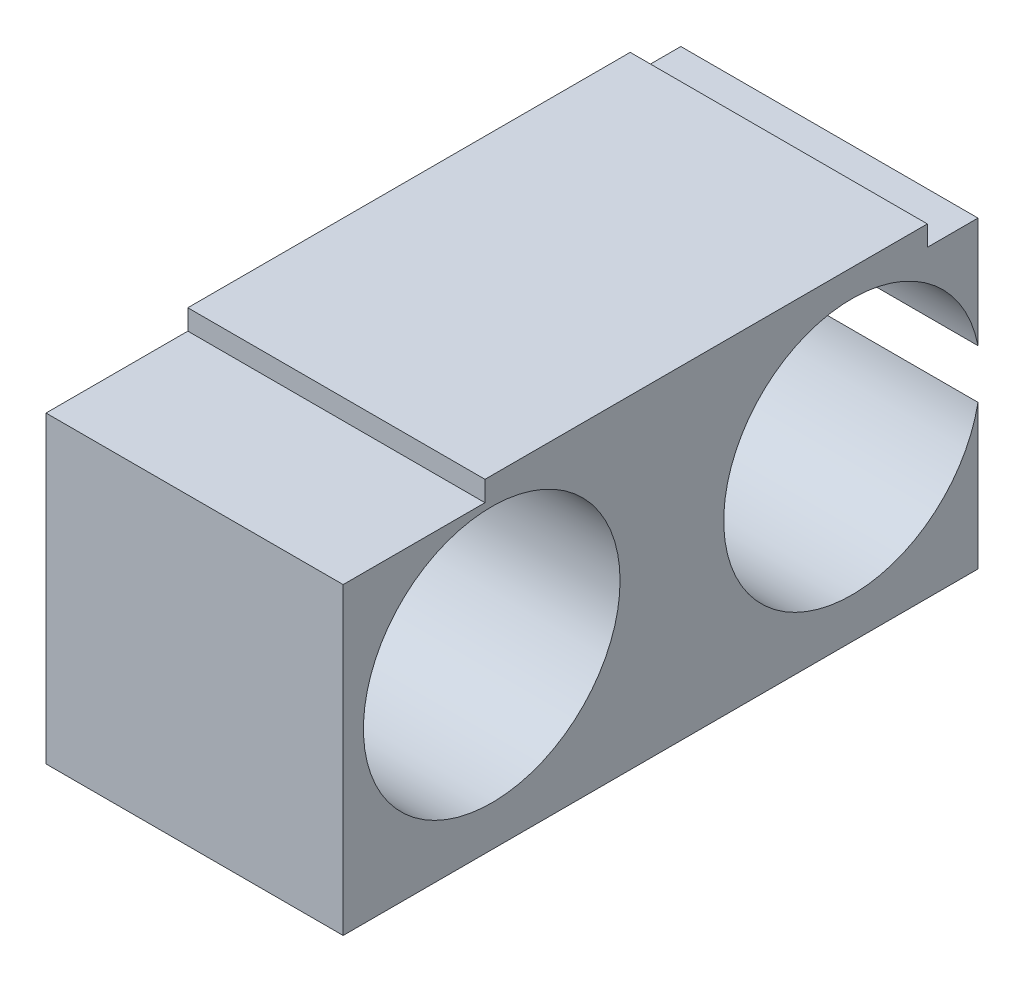
SolidWorks part; units mm, degrees
material "Pure Lead"
ref_plane "Front Plane" through (0, 0, 0) normal (0, 0, 1) x (1, 0, 0)
ref_plane "Top Plane" through (0, 0, 0) normal (0, 1, 0) x (1, 0, 0)
ref_plane "Right Plane" through (0, 0, 0) normal (1, 0, 0) x (0, 0, -1)
other "Lead Shot"
sketch "Sketch1" plane through (0, 0, 0) normal (0, 1, 0) x (1, 0, 0)
  line L1 (-22, -47) -> (22, -47)
  line L2 (-22, -47) -> (-22, 47)
  line L3 (-22, 47) -> (22, 47)
  line L4 (22, -47) -> (22, 47)
  line L5 (-22, -47) -> (22, 47) construction
  line L6 (-22, 47) -> (22, -47) construction
  point P0 (0, 0)
  dimension "D1" = 44
  dimension "D2" = 94
extrude "Boss-Extrude1" add sketch "Sketch1" along normal blind 48
sketch "Sketch2" plane through (22, 0, 0) normal (1, 0, 0) x (0, 0, -1)
  line L0 (-47, 48) -> (-47, 0) construction
  line L2 (-47, 48) -> (47, 48) construction
  circle A0 centre (-25, 25) radius 19
  circle A1 centre (28.35, 25) radius 19
  point P4 (-24.1101, 47.3482)
  dimension "D2" = 38
  dimension "D1" = 53.35
  dimension "D3" = 22
  dimension "D4" = 23
extrude "Cut-Extrude1" cut sketch "Sketch2" against normal through all
sketch "Sketch3" plane through (22, 0, 0) normal (1, 0, 0) x (0, 0, -1)
  line L1 (47, 48) -> (39.5, 48)
  line L2 (47, 48) -> (47, 45)
  line L3 (47, 45) -> (39.5, 45)
  line L4 (39.5, 48) -> (39.5, 45)
  line L5 (-47, 48) -> (-26, 48)
  line L6 (-47, 48) -> (-47, 45)
  line L7 (-47, 45) -> (-26, 45)
  line L8 (-26, 48) -> (-26, 45)
  point P4 (47, 48)
  point P9 (47, 51)
  point P10 (-47, 48)
  point P12 (0, 0)
  point P13 (0, 0)
  point P14 (48.1761, 52.9011)
  point P15 (0, 0)
  dimension "D1" = 3
  dimension "D2" = 7.5
  dimension "D3" = 21
extrude "Cut-Extrude2" cut sketch "Sketch3" against normal through all
